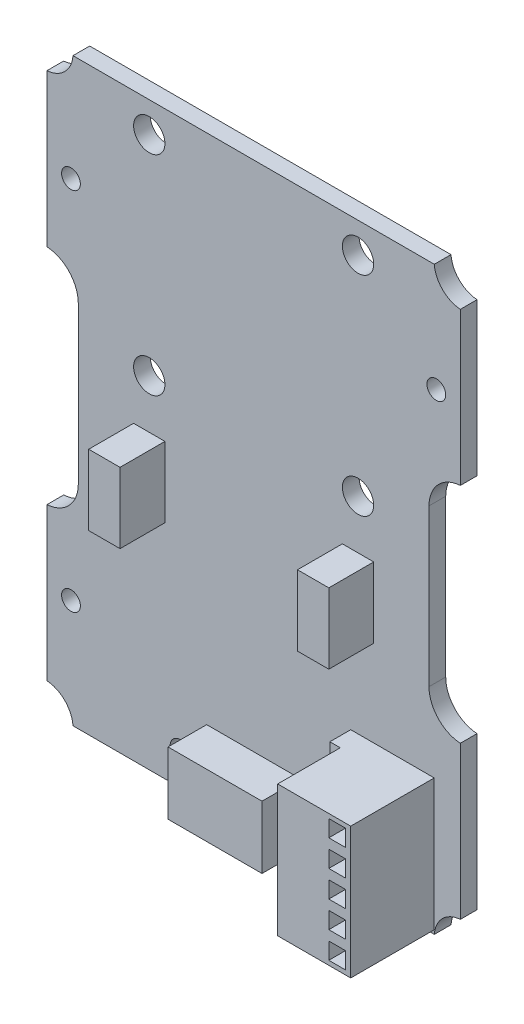
SolidWorks part; units mm, degrees
ref_plane "前视基准面" through (0, 0, 0) normal (0, 0, 1) x (1, 0, 0)
ref_plane "上视基准面" through (0, 0, 0) normal (0, 1, 0) x (1, 0, 0)
ref_plane "右视基准面" through (0, 0, 0) normal (1, 0, 0) x (0, 0, -1)
sketch "Model" plane through (0, 0, 0) normal (0, 0, 1) x (1, 0, 0)
  line L0 (-17.5, -19.4) -> (-20, -19.4)
  line L1 (-17.5, -28) -> (17.5, -28)
  line L2 (20, -25.5) -> (20, -10.5)
  line L3 (17, 7.5) -> (17, -7.5)
  line L4 (17.5, 15.6) -> (20, 15.6)
  line L5 (17.5, 19.4) -> (20, 19.4)
  line L6 (20, 10.5) -> (20, 25.5)
  line L7 (17.5, 28) -> (-17.5, 28)
  line L8 (-20, 19.4) -> (-17.5, 19.4)
  line L9 (-17.5, 15.6) -> (-20, 15.6)
  line L10 (-20, 25.5) -> (-20, 10.5)
  line L11 (-17, -7.5) -> (-17, 7.5)
  line L12 (-20, -10.5) -> (-20, -25.5)
  line L13 (-20, -15.6) -> (-17.5, -15.6)
  line L14 (16.8, -16.84) -> (15.2, -16.84)
  line L15 (15.2, -16.84) -> (15.2, -15.24)
  line L16 (16.8, -15.24) -> (15.2, -15.24)
  line L17 (16.8, -16.84) -> (16.8, -15.24)
  line L18 (16.8, -19.38) -> (15.2, -19.38)
  line L19 (15.2, -19.38) -> (15.2, -17.78)
  line L20 (16.8, -17.78) -> (15.2, -17.78)
  line L21 (16.8, -19.38) -> (16.8, -17.78)
  line L22 (16.8, -21.92) -> (15.2, -21.92)
  line L23 (15.2, -21.92) -> (15.2, -20.32)
  line L24 (16.8, -20.32) -> (15.2, -20.32)
  line L25 (16.8, -21.92) -> (16.8, -20.32)
  line L26 (16.8, -24.46) -> (15.2, -24.46)
  line L27 (15.2, -24.46) -> (15.2, -22.86)
  line L28 (16.8, -22.86) -> (15.2, -22.86)
  line L29 (16.8, -24.46) -> (16.8, -22.86)
  line L30 (16.8, -27) -> (15.2, -27)
  line L31 (15.2, -27) -> (15.2, -25.4)
  line L32 (16.8, -25.4) -> (15.2, -25.4)
  line L33 (16.8, -27) -> (16.8, -25.4)
  arc A0 (-17.5, -28) -> (-20, -25.5) centre (-20, -28) ccw
  arc A1 (20, -25.5) -> (17.5, -28) centre (20, -28) ccw
  arc A2 (17, -7.5) -> (20, -10.5) centre (20, -7.5) ccw
  arc A3 (20, 10.5) -> (17, 7.5) centre (20, 7.5) ccw
  arc A4 (17.5, 19.4) -> (17.5, 15.6) centre (17.5, 17.5) ccw
  arc A5 (17.5, 28) -> (20, 25.5) centre (20, 28) ccw
  arc A6 (-20, 25.5) -> (-17.5, 28) centre (-20, 28) ccw
  arc A7 (-17.5, 15.6) -> (-17.5, 19.4) centre (-17.5, 17.5) ccw
  arc A8 (-17, 7.5) -> (-20, 10.5) centre (-20, 7.5) ccw
  arc A9 (-20, -10.5) -> (-17, -7.5) centre (-20, -7.5) ccw
  arc A10 (-17.5, -19.4) -> (-17.5, -15.6) centre (-17.5, -17.5) ccw
  circle A11 centre (-17.5, 17.5) radius 0.9
  circle A12 centre (-17.5, 17.5) radius 0.9
  circle A13 centre (17.5, 17.5) radius 0.9
  circle A14 centre (-17.5, -17.5) radius 0.9
sketch "草图2" plane through (0, 0, 0) normal (0, 0, 1) x (1, 0, 0)
  line L0 (-20, -15.6) -> (-17.5, -15.6) construction
  line L1 (-17.5, -19.4) -> (-20, -19.4) construction
  line L2 (-20, 19.4) -> (-17.5, 19.4) construction
  line L3 (-17.5, 15.6) -> (-20, 15.6) construction
  line L4 (15.2, -16.84) -> (16.8, -16.84)
  line L5 (15.2, -15.24) -> (15.2, -16.84)
  line L6 (16.8, -15.24) -> (15.2, -15.24)
  line L7 (16.8, -16.84) -> (16.8, -15.24)
  line L8 (20, 10.5) -> (20, 25.5)
  line L9 (17, -7.5) -> (17, 7.5)
  line L10 (20, -25.5) -> (20, -10.5)
  line L11 (-17.5, -28) -> (17.5, -28)
  line L12 (-20, -10.5) -> (-20, -25.5)
  line L13 (-17, 7.5) -> (-17, -7.5)
  line L14 (-20, 25.5) -> (-20, 10.5)
  line L15 (17.5, 28) -> (-17.5, 28)
  line L16 (20, 10.5) -> (20, 25.5) construction
  line L17 (17, -7.5) -> (17, 7.5) construction
  line L18 (20, -25.5) -> (20, -10.5) construction
  line L19 (-17.5, -28) -> (17.5, -28) construction
  line L20 (-20, -10.5) -> (-20, -25.5) construction
  line L21 (-17, 7.5) -> (-17, -7.5) construction
  line L22 (-20, 25.5) -> (-20, 10.5) construction
  line L23 (17.5, 28) -> (-17.5, 28) construction
  line L24 (15.2, -16.84) -> (16.8, -16.84)
  line L25 (15.2, -15.24) -> (15.2, -16.84)
  line L26 (16.8, -15.24) -> (15.2, -15.24)
  line L27 (16.8, -16.84) -> (16.8, -15.24)
  line L28 (15.2, -27) -> (16.8, -27)
  line L29 (15.2, -25.4) -> (15.2, -27)
  line L30 (16.8, -25.4) -> (15.2, -25.4)
  line L31 (16.8, -27) -> (16.8, -25.4)
  line L32 (15.2, -27) -> (16.8, -27)
  line L33 (15.2, -25.4) -> (15.2, -27)
  line L34 (16.8, -25.4) -> (15.2, -25.4)
  line L35 (16.8, -27) -> (16.8, -25.4)
  line L36 (15.2, -24.46) -> (16.8, -24.46)
  line L37 (15.2, -22.86) -> (15.2, -24.46)
  line L38 (16.8, -22.86) -> (15.2, -22.86)
  line L39 (16.8, -24.46) -> (16.8, -22.86)
  line L40 (15.2, -24.46) -> (16.8, -24.46)
  line L41 (15.2, -22.86) -> (15.2, -24.46)
  line L42 (16.8, -22.86) -> (15.2, -22.86)
  line L43 (16.8, -24.46) -> (16.8, -22.86)
  line L44 (15.2, -21.92) -> (16.8, -21.92)
  line L45 (15.2, -20.32) -> (15.2, -21.92)
  line L46 (16.8, -20.32) -> (15.2, -20.32)
  line L47 (16.8, -21.92) -> (16.8, -20.32)
  line L48 (15.2, -21.92) -> (16.8, -21.92)
  line L49 (15.2, -20.32) -> (15.2, -21.92)
  line L50 (16.8, -20.32) -> (15.2, -20.32)
  line L51 (16.8, -21.92) -> (16.8, -20.32)
  line L52 (15.2, -17.78) -> (15.2, -19.38)
  line L53 (16.8, -17.78) -> (15.2, -17.78)
  line L54 (16.8, -19.38) -> (16.8, -17.78)
  line L55 (15.2, -19.38) -> (16.8, -19.38)
  line L56 (15.2, -17.78) -> (15.2, -19.38)
  line L57 (16.8, -17.78) -> (15.2, -17.78)
  line L58 (16.8, -19.38) -> (16.8, -17.78)
  line L59 (15.2, -19.38) -> (16.8, -19.38)
  line L60 (17.5, 15.6) -> (20, 15.6) construction
  line L61 (17.5, 19.4) -> (20, 19.4) construction
  line L62 (-20, -15.6) -> (-17.5, -15.6)
  line L63 (-17.5, -19.4) -> (-20, -19.4)
  line L64 (-20, 19.4) -> (-17.5, 19.4)
  line L65 (-17.5, 15.6) -> (-20, 15.6)
  line L66 (17.5, 15.6) -> (20, 15.6)
  line L67 (17.5, 19.4) -> (20, 19.4)
  line L68 (19.8, 10.6937) -> (19.8, 25.3074)
  line L69 (17.3074, 27.8) -> (-17.3074, 27.8)
  line L70 (-19.8, 25.3074) -> (-19.8, 10.6937)
  line L71 (-16.8, 7.5) -> (-16.8, -7.5)
  line L72 (-19.8, -10.6937) -> (-19.8, -25.3074)
  line L73 (-17.3074, -27.8) -> (17.3074, -27.8)
  line L74 (19.8, -25.3074) -> (19.8, -10.6937)
  line L75 (16.8, -7.5) -> (16.8, 7.5)
  arc A0 (-17.5, -19.4) -> (-17.5, -15.6) centre (-17.5, -17.5) ccw construction
  circle A1 centre (-17.5, -17.5) radius 0.9
  circle A2 centre (-17.5, -17.5) radius 0.9
  circle A3 centre (17.5, 17.5) radius 0.9
  circle A4 centre (17.5, 17.5) radius 0.9
  circle A5 centre (-17.5, 17.5) radius 0.9
  circle A6 centre (-17.5, 17.5) radius 0.9
  circle A7 centre (-17.5, 17.5) radius 0.9
  arc A8 (20, 10.5) -> (17, 7.5) centre (20, 7.5) ccw
  arc A9 (17, -7.5) -> (20, -10.5) centre (20, -7.5) ccw
  arc A10 (20, -25.5) -> (17.5, -28) centre (20, -28) ccw
  arc A11 (-17.5, -28) -> (-20, -25.5) centre (-20, -28) ccw
  arc A12 (-20, -10.5) -> (-17, -7.5) centre (-20, -7.5) ccw
  arc A13 (-17, 7.5) -> (-20, 10.5) centre (-20, 7.5) ccw
  arc A14 (-20, 25.5) -> (-17.5, 28) centre (-20, 28) ccw
  arc A15 (17.5, 28) -> (20, 25.5) centre (20, 28) ccw
  arc A16 (20, 10.5) -> (17, 7.5) centre (20, 7.5) ccw construction
  arc A17 (17, -7.5) -> (20, -10.5) centre (20, -7.5) ccw construction
  arc A18 (20, -25.5) -> (17.5, -28) centre (20, -28) ccw construction
  arc A19 (-17.5, -28) -> (-20, -25.5) centre (-20, -28) ccw construction
  arc A20 (-20, -10.5) -> (-17, -7.5) centre (-20, -7.5) ccw construction
  arc A21 (-17, 7.5) -> (-20, 10.5) centre (-20, 7.5) ccw construction
  arc A22 (-20, 25.5) -> (-17.5, 28) centre (-20, 28) ccw construction
  arc A23 (17.5, 28) -> (20, 25.5) centre (20, 28) ccw construction
  circle A24 centre (-17.5, 17.5) radius 0.9
  arc A25 (-17.5, 15.6) -> (-17.5, 19.4) centre (-17.5, 17.5) ccw construction
  arc A26 (17.5, 19.4) -> (17.5, 15.6) centre (17.5, 17.5) ccw construction
  arc A27 (-17.5, -19.4) -> (-17.5, -15.6) centre (-17.5, -17.5) ccw
  arc A28 (-17.5, 15.6) -> (-17.5, 19.4) centre (-17.5, 17.5) ccw
  arc A29 (17.5, 19.4) -> (17.5, 15.6) centre (17.5, 17.5) ccw
  arc A30 (17.3074, 27.8) -> (19.8, 25.3074) centre (20, 28) ccw
  arc A31 (-19.8, 25.3074) -> (-17.3074, 27.8) centre (-20, 28) ccw
  arc A32 (-16.8, 7.5) -> (-19.8, 10.6937) centre (-20, 7.5) ccw
  arc A33 (-19.8, -10.6937) -> (-16.8, -7.5) centre (-20, -7.5) ccw
  arc A34 (-17.3074, -27.8) -> (-19.8, -25.3074) centre (-20, -28) ccw
  arc A35 (19.8, -25.3074) -> (17.3074, -27.8) centre (20, -28) ccw
  arc A36 (16.8, -7.5) -> (19.8, -10.6937) centre (20, -7.5) ccw
  arc A37 (19.8, 10.6937) -> (16.8, 7.5) centre (20, 7.5) ccw
  dimension "D1" = 0
  dimension "D2" = 0
  dimension "D3" = 0
  dimension "D4" = 0
  dimension "D5" = 0
  dimension "D6" = 0
  dimension "D7" = 0
  dimension "D8" = 0
  dimension "D9" = 0
  dimension "D10" = 0
  dimension "D11" = 0.2
extrude "凸台-拉伸1" add sketch "草图2" along normal blind 1.6 contours L69 A31 L70 A32 L71 A33 L72 A34 L73 A35 L74 A36 L75 A37 L68 A30
extrude "切除-拉伸4" cut sketch "草图2<3>" along normal through all contours A4 | A6 | A2 | L24 L27 L26 L25 | L56 L59 L58 L57 | L48 L51 L50 L49 | L40 L43 L42 L41 | L32 L35 L34 L33 region at (16, -16.04, 0) region at (16, -26.2, 0) region at (16, -23.66, 0) region at (16, -21.12, 0) region at (16, -18.58, 0) region at (-17.5, -17.5, 0) region at (17.5, 17.5, 0) region at (-17.5, 17.5, 0)
sketch "草图2<3>" plane through (0, 0, 0) normal (0, 0, 1) x (1, 0, 0) same geometry as "草图2"
sketch "草图3" plane through (0, 0, 1.6) normal (0, 0, 1) x (1, 0, 0)
  line L1 (-4.5, -27.3) -> (4.5, -27.3)
  line L2 (-4.5, -27.3) -> (-4.5, -21.3)
  line L3 (-4.5, -21.3) -> (4.5, -21.3)
  line L4 (4.5, -27.3) -> (4.5, -21.3)
  line L5 (-17.3074, -27.8) -> (17.3074, -27.8) construction
  point P4 (0, -27.3)
  dimension "D1" = 9
  dimension "D2" = 6
  dimension "D3" = 0.5
extrude "凸台-拉伸2" add sketch "草图3" along normal blind 3.7
sketch "草图4" plane through (0, 0, 1.6) normal (0, 0, 1) x (1, 0, 0)
  line L0 (0, -0.88) -> (0, 0.88) construction
  line L2 (17.3074, 27.8) -> (-17.3074, 27.8) construction
  line L3 (-12.5, 2.4) -> (12.5, 2.4)
  line L4 (-12.5, 2.4) -> (-12.5, 27.4)
  line L5 (-12.5, 27.4) -> (12.5, 27.4)
  line L6 (12.5, 2.4) -> (12.5, 27.4)
  line L7 (-12.5, 2.4) -> (12.5, 27.4) construction
  line L8 (-12.5, 27.4) -> (12.5, 2.4) construction
  circle A0 centre (10, 24.9) radius 1.5
  circle A1 centre (10, 4.9) radius 1.5
  circle A2 centre (-10, 4.9) radius 1.5
  circle A3 centre (-10, 24.9) radius 1.5
  point P4 (0, 14.9)
  point P17 (0, 0)
  dimension "D1" = 3
  dimension "D2" = 3
  dimension "D3" = 20
  dimension "D4" = 20
  dimension "D5" = 0.4
  dimension "D6" = 25
extrude "切除-拉伸5" cut sketch "草图4" against normal through all contours A3 | A0 | A2 | A1 region at (10, 24.9, 1.6) region at (10, 4.9, 1.6) region at (-10, 4.9, 1.6) region at (-10, 24.9, 1.6)
sketch "草图6" plane through (0, 0, 1.6) normal (0, 0, 1) x (1, 0, 0)
  line L0 (-17.3074, -27.8) -> (17.3074, -27.8) construction
  line L1 (-14, -12.3) -> (14, -12.3)
  line L2 (-14, -12.3) -> (-14, 1.2)
  line L3 (-14, 1.2) -> (14, 1.2)
  line L4 (14, -12.3) -> (14, 1.2)
  point P4 (0, -12.3)
  dimension "D1" = 13.5
  dimension "D2" = 28
  dimension "D3" = 29
sketch "草图8" plane through (0, 0, 1.6) normal (0, 0, 1) x (1, 0, 0)
  line L0 (16.8, -21.92) -> (16.8, -20.32) construction
  line L1 (9.3, -14.82) -> (17.3, -14.82)
  line L2 (9.3, -14.82) -> (9.3, -27.42)
  line L3 (9.3, -27.42) -> (17.3, -27.42)
  line L4 (17.3, -14.82) -> (17.3, -27.42)
  line L5 (15.2, -27) -> (16.8, -27) construction
  line L6 (16.8, -27) -> (16.8, -25.4) construction
  line L7 (15.2, -24.46) -> (16.8, -24.46) construction
  line L8 (16.8, -24.46) -> (16.8, -22.86) construction
  line L9 (15.2, -21.92) -> (16.8, -21.92) construction
  line L10 (15.2, -19.38) -> (16.8, -19.38) construction
  line L11 (16.8, -19.38) -> (16.8, -17.78) construction
  line L12 (15.2, -16.84) -> (16.8, -16.84) construction
  line L13 (15.2, -25.4) -> (15.2, -27) construction
  line L14 (16.8, -25.4) -> (15.2, -25.4) construction
  line L15 (15.2, -22.86) -> (15.2, -24.46) construction
  line L16 (16.8, -22.86) -> (15.2, -22.86) construction
  line L17 (15.2, -20.32) -> (15.2, -21.92) construction
  line L18 (16.8, -20.32) -> (15.2, -20.32) construction
  line L19 (15.2, -17.78) -> (15.2, -19.38) construction
  line L20 (16.8, -17.78) -> (15.2, -17.78) construction
  line L21 (15.2, -15.24) -> (15.2, -16.84) construction
  line L22 (16.8, -16.84) -> (16.8, -15.24) construction
  line L23 (16.8, -15.24) -> (15.2, -15.24) construction
  line L24 (15.2, -27) -> (16.8, -27)
  line L25 (16.8, -27) -> (16.8, -25.4)
  line L26 (15.2, -24.46) -> (16.8, -24.46)
  line L27 (16.8, -24.46) -> (16.8, -22.86)
  line L28 (15.2, -21.92) -> (16.8, -21.92)
  line L29 (16.8, -21.92) -> (16.8, -20.32)
  line L30 (15.2, -19.38) -> (16.8, -19.38)
  line L31 (16.8, -19.38) -> (16.8, -17.78)
  line L32 (15.2, -16.84) -> (16.8, -16.84)
  line L33 (15.2, -25.4) -> (15.2, -27)
  line L34 (16.8, -25.4) -> (15.2, -25.4)
  line L35 (15.2, -22.86) -> (15.2, -24.46)
  line L36 (16.8, -22.86) -> (15.2, -22.86)
  line L37 (15.2, -20.32) -> (15.2, -21.92)
  line L38 (16.8, -20.32) -> (15.2, -20.32)
  line L39 (15.2, -17.78) -> (15.2, -19.38)
  line L40 (16.8, -17.78) -> (15.2, -17.78)
  line L41 (15.2, -15.24) -> (15.2, -16.84)
  line L42 (16.8, -16.84) -> (16.8, -15.24)
  line L43 (16.8, -15.24) -> (15.2, -15.24)
  point P4 (16.8, -21.12)
  point P5 (9.3, -21.12)
  point P8 (0, 0)
  dimension "D1" = 8
  dimension "D2" = 12.6
  dimension "D3" = 0.5
extrude "凸台-拉伸7" add sketch "草图8" along normal blind 8
sketch "草图9" plane through (0, 0, 1.6) normal (0, 0, 1) x (1, 0, 0)
  line L0 (0, -0.88) -> (0, 0.88) construction
  line L1 (-8.5, -6.55) -> (-11.5, -6.55)
  line L2 (-8.5, -6.55) -> (-8.5, 0.2)
  line L3 (-8.5, 0.2) -> (-11.5, 0.2)
  line L4 (-11.5, -6.55) -> (-11.5, 0.2)
  line L5 (8.5, 0.2) -> (11.5, 0.2)
  line L6 (11.5, -6.55) -> (11.5, 0.2)
  line L7 (8.5, -6.55) -> (11.5, -6.55)
  line L8 (8.5, -6.55) -> (8.5, 0.2)
  line L9 (-14, 1.2) -> (14, 1.2) construction
  dimension "D1" = 3
  dimension "D2" = 6.75
  dimension "D3" = 20
  dimension "D4" = 1
extrude "凸台-拉伸9" add sketch "草图9" along normal blind 4.3
sketch "草图10" plane through (0, 0, 1.6) normal (0, 0, 1) x (1, 0, 0)
  line L0 (0, -0.88) -> (0, 0.88) construction
  line L9 (-17.3074, -27.8) -> (17.3074, -27.8) construction
  circle A0 centre (-7, -24.8) radius 1
  circle A1 centre (7, -24.8) radius 1
  dimension "D1" = 2
  dimension "D2" = 14
  dimension "D3" = 3
extrude "切除-拉伸6" cut sketch "草图10" against normal through all
sketch "草图11" plane through (0, -27.42, 0) normal (0, -1, 0) x (1, 0, 0)
  line L1 (9.3, 9.6) -> (10.3, 9.6)
  line L2 (9.3, 9.6) -> (9.3, 3.6)
  line L3 (9.3, 3.6) -> (10.3, 3.6)
  line L4 (10.3, 9.6) -> (10.3, 3.6)
  dimension "D1" = 1
  dimension "D2" = 6
extrude "切除-拉伸7" cut sketch "草图11" against normal up to surface (12.6 mm away) up to face at (13.3, -14.82, 5.6)
